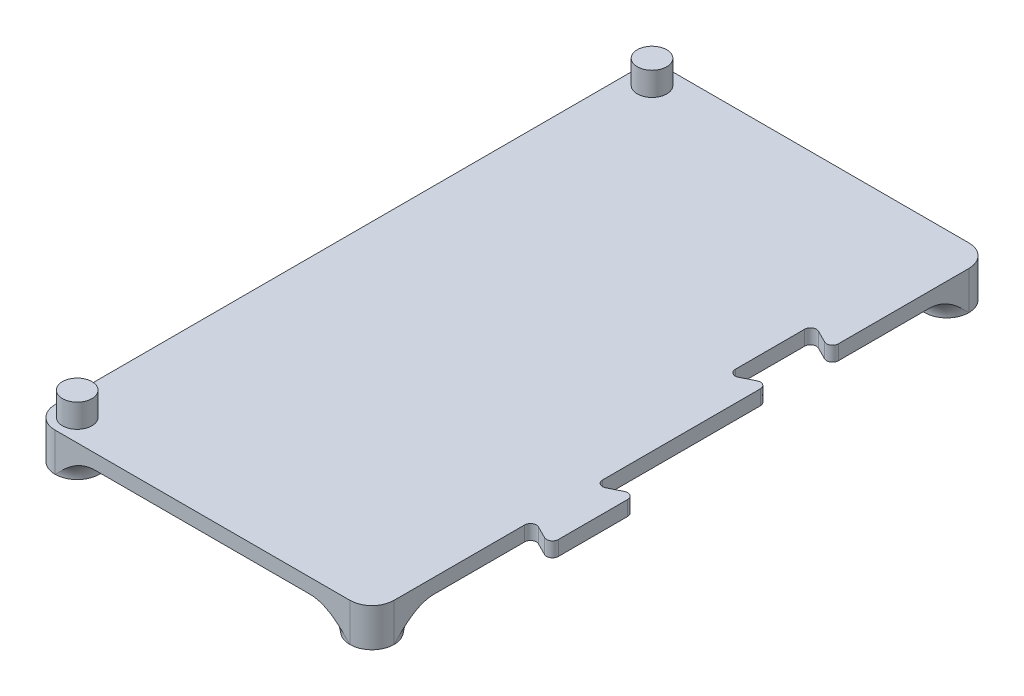
SolidWorks part; units mm, degrees
note: The reader was unsure of these and kept them because the rebuilt part matched: shared geometry of "Эскиз1<3>", "Эскиз1<4>", "Эскиз1<5>".
ref_plane "Спереди" through (0, 0, 0) normal (0, 0, 1) x (1, 0, 0)
ref_plane "Сверху" through (0, 0, 0) normal (0, 1, 0) x (1, 0, 0)
ref_plane "Справа" through (0, 0, 0) normal (1, 0, 0) x (0, 0, -1)
other "Configuration Table"
sketch "Эскиз1" plane through (0, 0, 0) normal (0, 1, 0) x (1, 0, 0)
  line L0 (0, 105) -> (0, -110.1763) construction
  line L1 (-50, -105) -> (50, -105)
  line L2 (-57.5, -97.5) -> (-57.5, 97.5)
  line L3 (-50, 105) -> (50, 105)
  line L4 (57.5, -97.5) -> (57.5, 97.5)
  line L5 (47.5, 55) -> (57.5, 50)
  line L7 (-57.5, 0) -> (57.5, 0) construction
  line L10 (47.5, 55) -> (47.5, 25)
  line L14 (67.5, -25) -> (67.5, -55)
  line L15 (47.5, 25) -> (57.5, 30)
  line L16 (67.5, -25) -> (57.5, -30)
  line L17 (67.5, -55) -> (57.5, -50)
  circle A0 centre (-50, -97.5) radius 7.5
  circle A1 centre (50, -97.5) radius 7.5
  circle A2 centre (50, 97.5) radius 7.5
  circle A3 centre (-50, 97.5) radius 7.5
  circle A4 centre (-50, -97.5) radius 5
  circle A5 centre (50, -97.5) radius 5
  circle A6 centre (50, 97.5) radius 5
  circle A7 centre (-50, 97.5) radius 5
  point P0 (0, 0)
  dimension "D3" = 15
  dimension "D4" = 10
  dimension "D1" = 210
  dimension "D2" = 115
  dimension "D5" = 50
  dimension "D6" = 20
  dimension "D7" = 5
  dimension "D8" = 5
  dimension "D9" = 10
  dimension "D10" = 50
  dimension "D11" = 5
  dimension "D12" = 20
  dimension "D13" = 5
  dimension "D14" = 10
extrude "Бобышка-Вытянуть1" add sketch "Эскиз1" along normal blind 5 contours A7 | A3 A7 | A6 | A2 A6 | A5 | A1 A5 | L3 A3 L2 A0 L1 A1 L4 A2 | A0 A4 | A4
extrude "Бобышка-Вытянуть2" add sketch "Эскиз1<3>" along normal blind 13 contours A4
sketch "Эскиз1<3>" plane through (0, 0, 0) normal (0, 1, 0) x (1, 0, 0) same geometry as "Эскиз1"
extrude "Бобышка-Вытянуть3" add sketch "Эскиз1<4>" against normal blind 8 contours A0 A4
sketch "Эскиз1<4>" plane through (0, 0, 0) normal (0, 1, 0) x (1, 0, 0) same geometry as "Эскиз1"
fillet "Скругление1" radius 8 1 edges at (-44.6967, 0, 92.1967)
mirror "Зеркальное отражение4" about plane through (0, 0, 0) normal (1, 0, 0) of "Бобышка-Вытянуть3"
mirror "Зеркальное отражение5" about plane through (0, 0, 0) normal (0, 0, 1) of "Зеркальное отражение4", "Бобышка-Вытянуть3"
fillet "Скругление2" radius 8 1 edges at (44.6967, 0, 92.1967)
fillet "Скругление3" radius 8 1 edges at (44.6967, 0, -92.1967)
fillet "Скругление4" radius 8 1 edges at (-44.6967, 0, -92.1967)
mirror "Зеркальное отражение6" about plane through (0, 0, 0) normal (0, 0, 1) of "Бобышка-Вытянуть2"
extrude "Бобышка-Вытянуть4" add sketch "Эскиз1<5>" along normal blind 5
sketch "Эскиз1<5>" plane through (0, 0, 0) normal (0, 1, 0) x (1, 0, 0) same geometry as "Эскиз1"
fillet "Скругление5" radius 2 8 edges at (57.5, 2.5, 30) (47.5, 2.5, -25) (57.5, 2.5, 50) (67.5, 2.5, 55) (67.5, 2.5, 25) (57.5, 2.5, -30) (47.5, 2.5, -55) (57.5, 2.5, -50)
